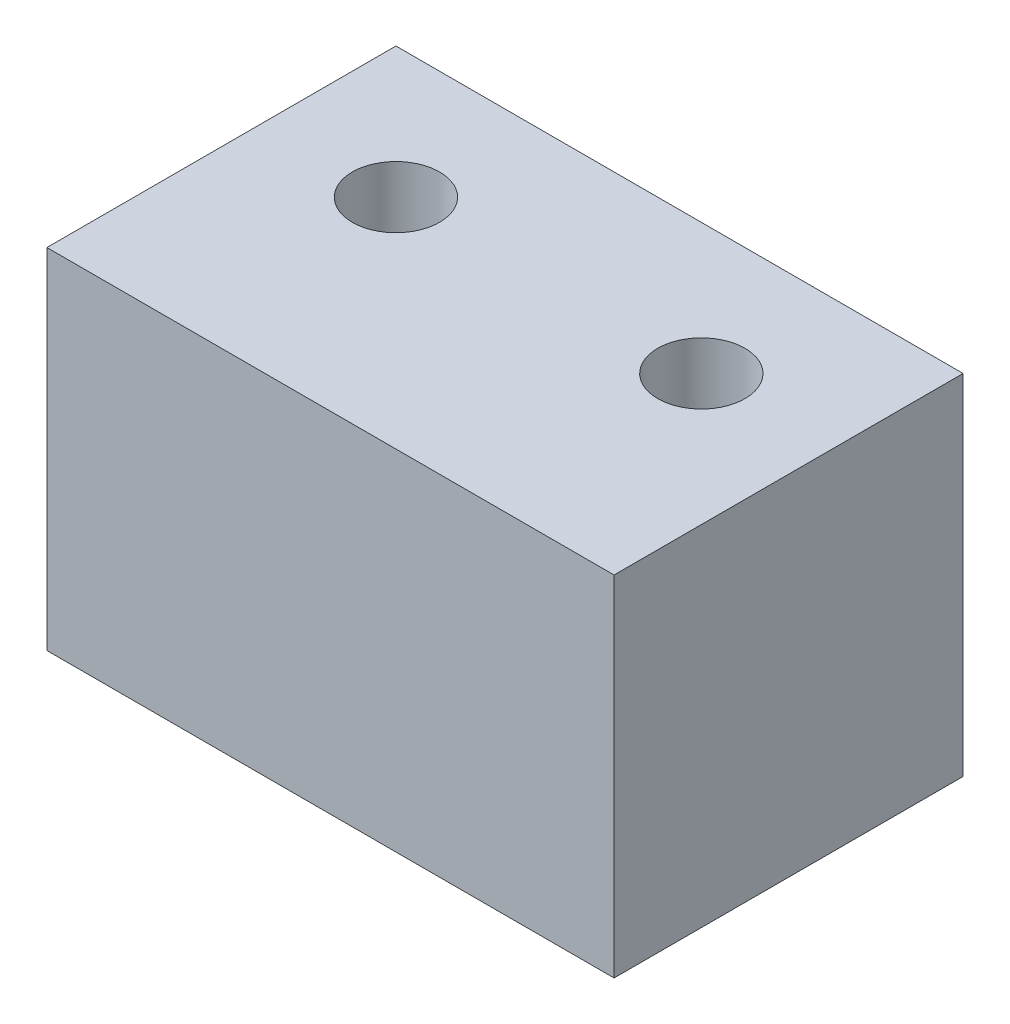
SolidWorks part; units mm, degrees
ref_plane "Front" through (0, 0, 0) normal (0, 0, 1) x (1, 0, 0)
ref_plane "Top" through (0, 0, 0) normal (0, 1, 0) x (1, 0, 0)
ref_plane "Right" through (0, 0, 0) normal (1, 0, 0) x (0, 0, -1)
sketch "Sketch1" plane through (0, 0, 0) normal (0, 1, 0) x (1, 0, 0)
  line L1 (-41.275, -25.4) -> (41.275, -25.4)
  line L2 (-41.275, -25.4) -> (-41.275, 25.4)
  line L3 (-41.275, 25.4) -> (41.275, 25.4)
  line L4 (41.275, -25.4) -> (41.275, 25.4)
  line L5 (-41.275, -25.4) -> (41.275, 25.4) construction
  line L6 (-41.275, 25.4) -> (41.275, -25.4) construction
  point P0 (0, 0)
  dimension "D1" = 82.55
  dimension "D2" = 50.8
extrude "Boss-Extrude1" add sketch "Sketch1" along normal mid plane 50.8 contours L3 L4 L1 L2
sketch "Sketch2" plane through (0, 25.4, 0) normal (0, 1, 0) x (1, 0, 0)
  line L0 (22.225, 6.35) -> (-22.225, 6.35) construction
  line L1 (0, -50) -> (0, 50) construction
  line L2 (-50, 0) -> (50, 0) construction
  point P0 (22.225, 6.35)
  point P1 (-22.225, 6.35)
  point P4 (0, 6.35)
  dimension "D1" = 44.45
  dimension "D2" = 6.35
hole_wizard "1/2 (0.5000) Dowel Hole1" positions "Sketch3" profile "Sketch5" hole size "1/2" standard "ANSI Inch" end condition through all
sketch "Sketch3" plane through (0, 25.4, 0) normal (0, 1, 0) x (1, 0, 0)
  point P0 (22.225, 6.35)
  point P3 (-22.225, 6.35)
sketch "Sketch5" plane through (22.225, 25.4, -6.35) normal (1, 0, 0) x (0, 0, 1)
  line L0 (0, 0) -> (0, 50.8)
  line L1 (0, 50.8) -> (6.35, 50.8)
  line L2 (6.35, 50.8) -> (6.35, 0)
  line L5 (6.35, 0) -> (0, 0)
  line L11 (0, -6.35) -> (0, 107.95) construction
  dimension "Thru Hole Dia." = 12.7
  dimension "Thru Hole Depth" = 50.8
sketch "Sketch6" plane through (-41.275, 0, 0) normal (-1, 0, 0) x (0, 0, 1)
  line L0 (0, 12.7) -> (0, -12.7) construction
  line L1 (50, 0) -> (-50, 0) construction
  line L2 (0, -50) -> (0, 50) construction
  point P0 (0, 12.7)
  point P1 (0, -12.7)
  point P4 (0, 0)
  dimension "D1" = 25.4
hole_wizard "1/4-20 Tapped Hole1" positions "Sketch7" profile "Sketch9" tap size "1/4-20" standard "ANSI Inch"
sketch "Sketch7" plane through (-41.275, 0, 0) normal (-1, 0, 0) x (0, 0, 1)
  point P0 (0, 12.7)
  point P3 (0, -12.7)
sketch "Sketch9" plane through (-41.275, 12.7, 0) normal (0, 1, 0) x (0, 0, 1)
  line L0 (0, 0) -> (0, 14.2338)
  line L1 (0, 14.2338) -> (2.5527, 12.7)
  line L2 (2.5527, 12.7) -> (2.5527, 0)
  line L5 (2.5527, 0) -> (0, 0)
  line L10 (0, 14.2338) -> (-2.5527, 12.7) construction
  line L11 (0, -6.35) -> (0, 107.95) construction
  dimension "Tap Drill Dia." = 5.1054
  dimension "Tap Drill Depth" = 12.7
  dimension "Drill Angle" = 118
cosmetic thread "Hole Thread1" parameters "D1"=12.7, "D2"=6.35
cosmetic thread "Hole Thread2" parameters "D1"=12.7, "D2"=6.35
sketch "Sketch10" plane through (0, 0, -25.4) normal (0, 0, -1) x (-1, 0, 0)
  line L0 (50, 0) -> (-50, 0) construction
  point P0 (-22.225, 0)
  point P1 (22.225, 0)
  point P2 (0, 0)
  point P5 (0, 0)
hole_wizard "1/4-20 Tapped Hole2" positions "Sketch11" profile "Sketch13" tap size "1/4-20" standard "ANSI Inch" end condition up to next
sketch "Sketch11" plane through (0, 0, -25.4) normal (0, 0, -1) x (-1, 0, 0)
  point P0 (-22.225, 0)
  point P3 (22.225, 0)
sketch "Sketch13" plane through (22.225, 0, -25.4) normal (1, 0, 0) x (0, 1, 0)
  line L0 (0, 0) -> (0, 12.7)
  line L1 (0, 12.7) -> (2.5527, 12.7)
  line L2 (2.5527, 12.7) -> (2.5527, 0)
  line L5 (2.5527, 0) -> (0, 0)
  line L11 (0, -6.35) -> (0, 107.95) construction
  dimension "Thru Tap Drill Dia." = 5.1054
  dimension "Thru Tap Drill Depth" = 12.7
cosmetic thread "Hole Thread3" parameters "D2"=6.35
cosmetic thread "Hole Thread4" parameters "D2"=6.35
